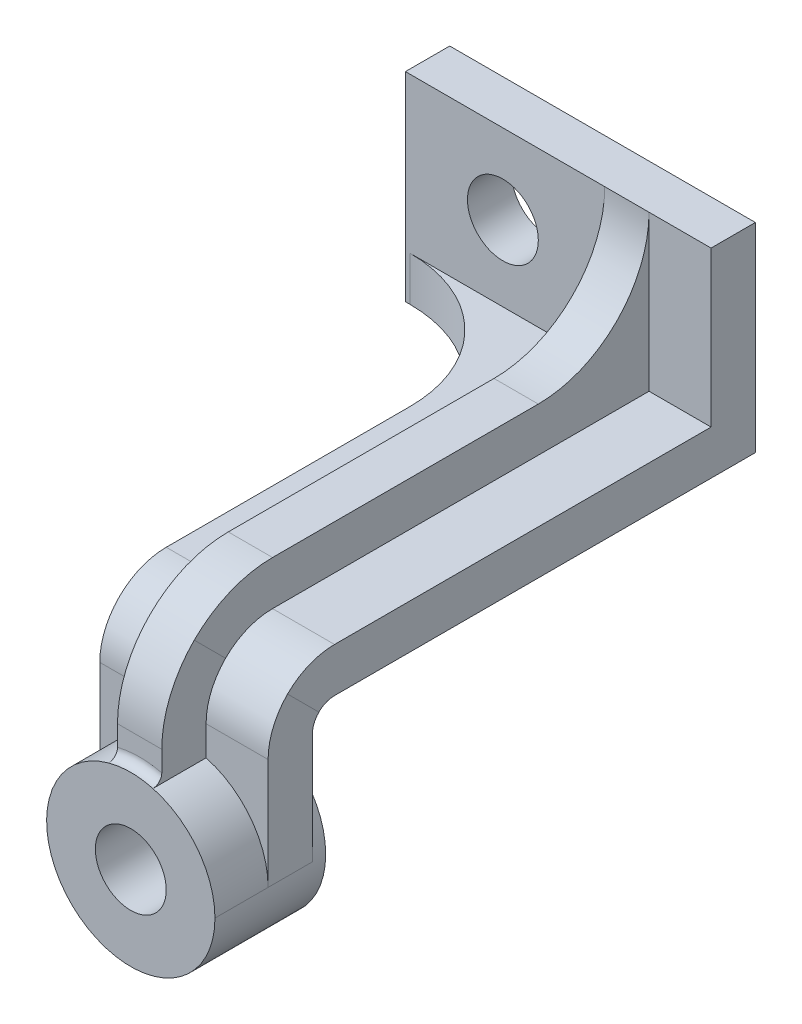
SolidWorks part; units mm, degrees
ref_plane "Front Plane" through (0, 0, 0) normal (0, 0, 1) x (1, 0, 0)
ref_plane "Top Plane" through (0, 0, 0) normal (0, 1, 0) x (1, 0, 0)
ref_plane "Right Plane" through (0, 0, 0) normal (1, 0, 0) x (0, 0, -1)
sketch "Sketch1" plane through (0, 0, 0) normal (0, 0, 1) x (1, 0, 0)
  line L1 (-34.5, 22.5) -> (34.5, 22.5)
  line L2 (-34.5, 22.5) -> (-34.5, -22.5)
  line L3 (-34.5, -22.5) -> (34.5, -22.5)
  line L4 (34.5, 22.5) -> (34.5, -22.5)
  line L5 (-34.5, 22.5) -> (34.5, -22.5) construction
  line L6 (-34.5, -22.5) -> (34.5, 22.5) construction
  point P0 (0, 0)
  dimension "D1" = 45
  dimension "D2" = 69
extrude "Boss-Extrude1" add sketch "Sketch1" along normal blind 10
ref_plane "Plane1" through (15.5, 0, 0) normal (1, 0, 0) x (0, 0, -1)
sketch "Sketch3" plane through (15.5, 0, 0) normal (1, 0, 0) x (0, 0, -1)
  line L0 (-10, -22.5) -> (-100, -22.5)
  line L1 (-100, -22.5) -> (-100, -52.5)
  line L2 (0, -22.5) -> (0, 22.5) construction
  dimension "D1" = 100
  dimension "D2" = 75
sketch "Sketch4" plane through (0, 0, 10) normal (0, 0, 1) x (1, 0, 0)
  line L0 (34.5, -22.5) -> (34.5, 22.5) construction
  line L1 (34.5, -22.5) -> (-3.5, -22.5)
  line L2 (34.5, -22.5) -> (34.5, -12.5)
  line L3 (34.5, -12.5) -> (20.5, -12.5)
  line L4 (-3.5, -22.5) -> (-3.5, -12.5)
  line L5 (34.5, -22.5) -> (-3.5, -12.5) construction
  line L6 (34.5, -12.5) -> (-3.5, -22.5) construction
  line L8 (20.5, -12.5) -> (20.5, -2.5)
  line L9 (20.5, -2.5) -> (10.5, -2.5)
  line L10 (10.5, -12.5) -> (10.5, -2.5)
  line L11 (20.5, -12.5) -> (10.5, -2.5) construction
  line L12 (20.5, -2.5) -> (10.5, -12.5) construction
  line L13 (10.5, -12.5) -> (-3.5, -12.5)
  point P4 (15.5, -17.5)
  point P10 (15.5, -7.5)
  dimension "D1" = 38
  dimension "D2" = 10
  dimension "D3" = 10
  dimension "D4" = 10
  dimension "D5" = 19
sweep "Sweep1" add profiles "Sketch4" path "Sketch3"
sketch "Sketch5" plane through (0, 0, 110) normal (0, 0, 1) x (1, 0, 0)
  line L0 (15.5, -22.5) -> (15.5, -52.5) construction
  circle A0 centre (15.5, -52.5) radius 19
extrude "Boss-Extrude2" add sketch "Sketch5" along normal blind 12 and the other way blind 13
sketch "Sketch6" plane through (0, 0, 122) normal (0, 0, 1) x (1, 0, 0)
  circle A0 centre (15.5, -52.5) radius 8
  dimension "D1" = 16
extrude "Cut-Extrude1" cut sketch "Sketch6" against normal through all
fillet "Fillet1" radius 25 1 edges at (15.5, -2.5, 120)
fillet "Fillet2" radius 15 2 edges at (27.5, -12.5, 110) (3.5, -12.5, 110)
fillet "Fillet3" radius 5 1 edges at (15.5, -22.5, 100)
fillet "Fillet4" radius 2 1 edges at (15.5, -33.5, 120)
fillet "Fillet5" radius 25 1 edges at (15.5, -2.5, 10)
fillet "Fillet6" radius 30 1 edges at (-3.5, -17.5, 10)
sketch "Sketch7" plane through (0, 0, 10) normal (0, 0, 1) x (1, 0, 0)
  line L0 (10.5, 22.5) -> (-34.5, 22.5) construction
  line L3 (-34.5, 22.5) -> (-34.5, -22.5) construction
  circle A0 centre (-12.5, 4.5) radius 8
  dimension "D3" = 16
  dimension "D1" = 18
  dimension "D2" = 22
extrude "Cut-Extrude2" cut sketch "Sketch7" against normal through all
